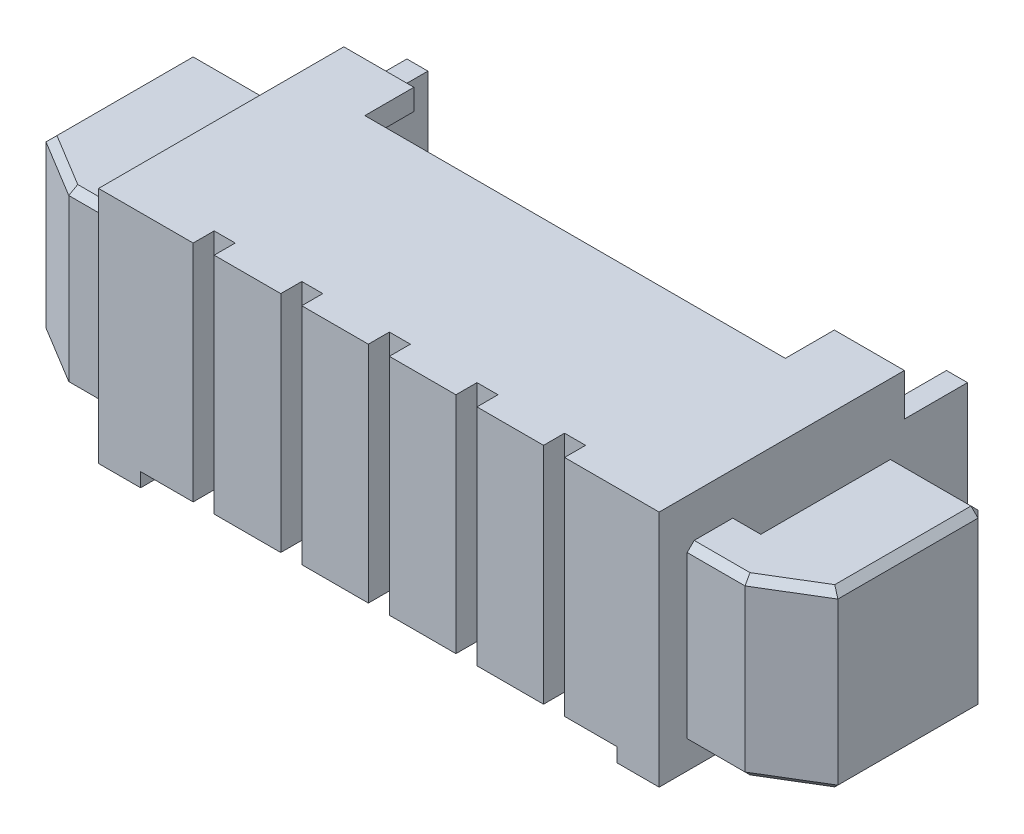
SolidWorks part; units mm, degrees
ref_plane "Front" through (0, 0, 0) normal (0, 0, 1) x (1, 0, 0)
ref_plane "Top" through (0, 0, 0) normal (0, 1, 0) x (1, 0, 0)
ref_plane "Right" through (0, 0, 0) normal (1, 0, 0) x (0, 0, -1)
sketch "Sketch2" plane through (0, 0, 0) normal (0, 1, 0) x (1, 0, 0)
  line L0 (-3.0934, -3.854) -> (1.9066, -3.854) construction
  dimension "D1" = 5
sketch "Sketch5" plane through (0, 0, 0) normal (0, 0, 1) x (1, 0, 0)
  line L0 (-2.4593, 1.3687) -> (2.5407, 1.3687) construction
  dimension "D1" = 5
sketch "Sketch1" plane through (0, 0, 0) normal (0, 1, 0) x (1, 0, 0)
  line L0 (0, -2.2) -> (0, 0) construction
  line L1 (-4, 0) -> (4, 0)
  line L2 (-4, 0) -> (-4, -4.4)
  line L3 (-4, -4.4) -> (4, -4.4)
  line L4 (4, 0) -> (4, -4.4)
  line L5 (0, -2.2) -> (3.0917, -2.2) construction
  dimension "D1" = 8
  dimension "D2" = 4.4
  dimension "D3" = 2.2
sketch "Sketch3" plane through (0, 0, 0) normal (0, 1, 0) x (1, 0, 0)
  line L0 (-2.1, 0) -> (-2.1, -1.6)
  line L1 (-4, 0) -> (4, 0) construction
  line L2 (-2.1, -1.6) -> (-2.35, -1.6)
  line L3 (-2.35, -1.6) -> (-2.35, -3.1)
  line L4 (-2.35, -3.1) -> (-1.35, -3.1)
  line L5 (-1.35, -3.1) -> (-1.35, -1.6)
  line L6 (-1.35, -1.6) -> (-1.6, -1.6)
  line L7 (-1.6, -1.6) -> (-1.6, 0)
  line L8 (-1.6, 0) -> (-2.1, 0)
  line L9 (0, 0) -> (0, 2.8139) construction
  line L10 (-1.85, 0) -> (-1.85, -0.5432) construction
  line L11 (-2.35, -4.1) -> (-1.4, -4.1) construction
  line L12 (-2.65, -4.1) -> (-2.35, -4.1)
  line L13 (-2.65, -4.1) -> (-2.65, -5.5)
  line L14 (-2.65, -5.5) -> (-2.35, -5.5)
  line L15 (-2.35, -4.1) -> (-2.35, -5.5)
  line L16 (-1.4, -4.1) -> (-1.1, -4.1)
  line L17 (-1.4, -4.1) -> (-1.4, -5.5)
  line L18 (-1.4, -5.5) -> (-1.1, -5.5)
  line L19 (-1.1, -4.1) -> (-1.1, -5.5)
  line L20 (-0.15, -4.1) -> (0.15, -4.1)
  line L21 (-0.15, -4.1) -> (-0.15, -5.5)
  line L22 (-0.15, -5.5) -> (0.15, -5.5)
  line L23 (0.15, -4.1) -> (0.15, -5.5)
  line L24 (1.1, -4.1) -> (1.4, -4.1)
  line L25 (1.1, -4.1) -> (1.1, -5.5)
  line L26 (1.1, -5.5) -> (1.4, -5.5)
  line L27 (1.4, -4.1) -> (1.4, -5.5)
  line L28 (2.35, -4.1) -> (2.65, -4.1)
  line L29 (2.35, -4.1) -> (2.35, -5.5)
  line L30 (2.35, -5.5) -> (2.65, -5.5)
  line L31 (2.65, -4.1) -> (2.65, -5.5)
  line L32 (-1.1, -4.1) -> (-0.15, -4.1) construction
  line L33 (0.15, -4.1) -> (1.1, -4.1) construction
  line L34 (1.4, -4.1) -> (2.35, -4.1) construction
  dimension "D1" = 0.5
  dimension "D2" = 1.6
  dimension "D3" = 1.6
  dimension "D4" = 1.5
  dimension "D5" = 1
  dimension "D6" = 1.25
  dimension "D7" = 0.3
  dimension "D8" = 5.5
  dimension "D9" = 1.4
extrude "Boss-Extrude1" add sketch "Sketch1" along normal blind 3.4
sketch "Sketch4" plane through (0, 0, 0) normal (0, -1, 0) x (1, 0, 0)
  line L0 (-4, 0) -> (-4, 4.4) construction
  line L1 (-3.4, 4.4) -> (3.4, 4.4)
  line L2 (-3.4, 4.4) -> (-3.4, 0)
  line L3 (-3.4, 0) -> (3.4, 0)
  line L4 (3.4, 4.4) -> (3.4, 0)
  line L5 (4, 0) -> (4, 4.4) construction
  line L6 (-4, 4.4) -> (4, 4.4) construction
  line L7 (-4, 0) -> (4, 0) construction
  dimension "D1" = 0.6
  dimension "D2" = 0.6
extrude "Cut-Extrude1" cut sketch "Sketch4" against normal blind 0.2
shell "Shell1" thickness 0.3 removed face at (0, 0.9, 0)
extrude "Cut-Extrude3" cut sketch "Sketch3" along normal up to next contours L7 L8 L0 L2 L3 L4 L5 L6 region at (-1.85, 0, 1.8109)
mirror "Mirror1" about plane through (0, 0, 0) normal (1, 0, 0) of "Cut-Extrude3"
sketch "Sketch8" plane through (0, 0, 4.1) normal (0, 0, -1) x (-1, 0, 0)
  line L4 (3.7, 0.5) -> (3.7, 3.1)
  line L5 (3.7, 3.1) -> (-3.7, 3.1)
  line L6 (-3.7, 3.1) -> (-3.7, 0.5)
  line L7 (-3.7, 0.5) -> (3.7, 0.5)
  line L8 (3.7, 0.5) -> (3.7, 3.1)
  line L9 (3.7, 3.1) -> (-3.7, 3.1)
  line L10 (-3.7, 3.1) -> (-3.7, 0.5)
  line L11 (-3.7, 0.5) -> (3.7, 0.5)
  dimension "D1" = 0
extrude "Boss-Extrude2" add sketch "Sketch8" along normal blind 0.3
extrude "Cut-Extrude4" cut sketch "Sketch3<3>" along normal through all contours L15 L12 L13 L14 | L19 L16 L17 L18 | L23 L20 L21 L22 | L27 L24 L25 L26 | L31 L28 L29 L30 region at (-2.5, 0, 4.8) region at (-1.25, 0, 4.8) region at (0, 0, 4.8) region at (1.25, 0, 4.8) region at (2.5, 0, 4.8)
sketch "Sketch3<3>" plane through (0, 0, 0) normal (0, 1, 0) x (1, 0, 0) same geometry as "Sketch3"
sketch "Sketch9" plane through (0, 0, 0) normal (0, 0, 1) x (1, 0, 0)
  line L0 (-2.65, 3.4) -> (-2.65, 0.2) construction
  line L1 (-2.35, 1.8) -> (-2.65, 1.8)
  line L2 (-2.35, 1.8) -> (-2.35, 1)
  line L3 (-2.35, 1) -> (-2.65, 1)
  line L4 (-2.65, 1.8) -> (-2.65, 1)
  line L5 (-2.35, 1.4) -> (-2.65, 1.4) construction
  line L6 (-4, 0) -> (4, 0) construction
  line L8 (-1.1, 1.8) -> (-1.4, 1.8)
  line L9 (-1.1, 1.8) -> (-1.1, 1)
  line L10 (-1.1, 1) -> (-1.4, 1)
  line L11 (-1.4, 1.8) -> (-1.4, 1)
  line L12 (0.15, 1.8) -> (-0.15, 1.8)
  line L13 (0.15, 1.8) -> (0.15, 1)
  line L14 (0.15, 1) -> (-0.15, 1)
  line L15 (-0.15, 1.8) -> (-0.15, 1)
  line L16 (1.4, 1.8) -> (1.1, 1.8)
  line L17 (1.4, 1.8) -> (1.4, 1)
  line L18 (1.4, 1) -> (1.1, 1)
  line L19 (1.1, 1.8) -> (1.1, 1)
  line L20 (2.65, 1.8) -> (2.35, 1.8)
  line L21 (2.65, 1.8) -> (2.65, 1)
  line L22 (2.65, 1) -> (2.35, 1)
  line L23 (2.35, 1.8) -> (2.35, 1)
  dimension "D1" = 1.4
  dimension "D2" = 0.8
  dimension "D3" = 0.3
  dimension "D5" = 5.3
  dimension "D4" = 5
extrude "Cut-Extrude5" cut sketch "Sketch9" along normal through all
sketch "Sketch10" plane through (0, 3.4, 0) normal (0, 1, 0) x (1, 0, 0)
  line L0 (4, -4.4) -> (4, 0) construction
  line L1 (-4, 0) -> (4, 0)
  line L2 (-4, 0) -> (-4, -0.9)
  line L3 (-4, -0.9) -> (4, -0.9)
  line L4 (4, 0) -> (4, -0.9)
  dimension "D1" = 3.5
extrude "Cut-Extrude6" cut sketch "Sketch10" against normal blind 0.6
sketch "Sketch11" plane through (0, 3.4, 0) normal (0, 1, 0) x (1, 0, 0)
  line L0 (-4, -0.9) -> (4, -0.9) construction
  line L1 (-3, -0.9) -> (3, -0.9)
  line L2 (-3, -0.9) -> (-3, -1.6)
  line L3 (-3, -1.6) -> (3, -1.6)
  line L4 (3, -0.9) -> (3, -1.6)
  line L5 (0, 0) -> (0, -2.0732) construction
  line L6 (4, -4.4) -> (4, -0.9) construction
  line L7 (1.4, -4.4) -> (2.35, -4.4) construction
  dimension "D1" = 1
  dimension "D2" = 2.8
extrude "Cut-Extrude7" cut sketch "Sketch11" against normal blind 1
sketch "Sketch12" plane through (0, 0, 0) normal (0, -1, 0) x (1, 0, 0)
  line L0 (4, 4) -> (4.825, 4)
  line L1 (4, 4.4) -> (4, 0) construction
  line L2 (4.825, 4) -> (5.65, 3.5)
  line L3 (5.65, 3.5) -> (5.65, 1.4)
  line L4 (5.65, 1.4) -> (4.3, 1.4)
  line L5 (4.3, 1.4) -> (4.3, 3.25)
  line L6 (4.3, 3.25) -> (4, 3.25)
  line L7 (4, 3.25) -> (4, 4)
  line L8 (4, 0) -> (3.4, 0) construction
  line L9 (0, 0) -> (0, 5.7519) construction
  line L10 (-1.6, 0) -> (1.6, 0) construction
  line L11 (4.825, 4) -> (5.65, 4) construction
  line L12 (5.65, 4) -> (5.65, 3.5) construction
  dimension "D1" = 2.6
  dimension "D2" = 4
  dimension "D3" = 11.3
  dimension "D4" = 0.5
  dimension "D5" = 1.85
  dimension "D6" = 0.3
extrude "Boss-Extrude3" add sketch "Sketch12" against normal blind 2.5 from offset 0.3 offset against normal yes
chamfer "Chamfer1" distance 0.1 angle 45 14 edges at (4.15, 0.3, 3.25) (4.3, 0.3, 2.325) (4.15, 2.8, 3.25) (4.3, 2.8, 2.325) (4.975, 2.8, 1.4) (4.975, 0.3, 1.4) (4.4125, 0.3, 4) (5.2375, 0.3, 3.75) (5.65, 0.3, 2.45) (5.65, 1.55, 1.4) (5.65, 2.8, 2.45) (5.2375, 2.8, 3.75) (4.4125, 2.8, 4) (4.3, 1.55, 1.4)
mirror "Mirror2" about plane through (0, 0, 0) normal (1, 0, 0) of "Chamfer1", "Boss-Extrude3"
